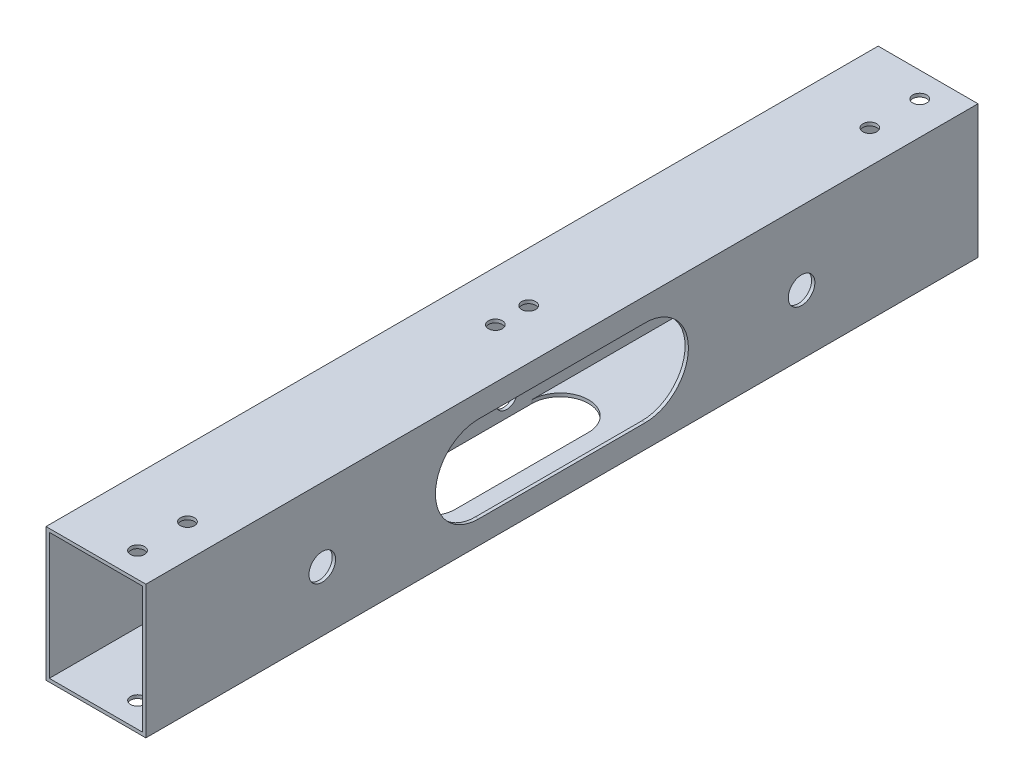
SolidWorks part; units mm, degrees
material "6061 合金"
ref_plane "前视基准面" through (0, 0, 0) normal (0, 0, 1) x (1, 0, 0)
ref_plane "上视基准面" through (0, 0, 0) normal (0, 1, 0) x (1, 0, 0)
ref_plane "右视基准面" through (0, 0, 0) normal (1, 0, 0) x (0, 0, -1)
other "Configuration Table"
sketch "草图1" plane through (0, 0, 0) normal (0, 0, 1) x (1, 0, 0)
  line L0 (15, -20) -> (15, 20)
  line L1 (15, 20) -> (-15, 20)
  line L2 (-15, 20) -> (-15, -20)
  line L3 (-15, -20) -> (15, -20)
  line L4 (14, 19) -> (-14, 19)
  line L5 (14, -19) -> (14, 19)
  line L6 (-14, -19) -> (14, -19)
  line L7 (-14, 19) -> (-14, -19)
extrude "凸台-拉伸1" add sketch "草图1" along normal blind 250
sketch "草图3" plane through (0, 20, 0) normal (0, 1, 0) x (1, 0, 0)
  line L0 (15, 0) -> (-15, 0) construction
  line L2 (-15, -125) -> (78.6025, -125) construction
  line L4 (-15, -250) -> (-15, 0) construction
  circle A0 centre (5, -7.5) radius 2.1
  circle A1 centre (5, -22.5) radius 2.1
  circle A4 centre (5, -227.5) radius 2.1
  circle A5 centre (5, -242.5) radius 2.1
  circle A6 centre (0, -120) radius 2.1
  circle A7 centre (0, -130) radius 2.1
  dimension "D1" = 4.2
  dimension "D2" = 7.5
  dimension "D4" = 20
  dimension "D5" = 4.2
  dimension "D6" = 10
  dimension "D3" = 2
extrude "切除-拉伸1" cut sketch "草图3" against normal blind 250
sketch "草图4" plane through (15, 0, 0) normal (1, 0, 0) x (0, 0, -1)
  line L0 (-250, 20) -> (0, 20) construction
  line L1 (0, -20) -> (0, 20) construction
  line L2 (-125, 20) -> (-125, -104.7599) construction
  circle A0 centre (-53, -2) radius 4
  circle A1 centre (-197, -2) radius 4
  dimension "D1" = 8
  dimension "D2" = 22
  dimension "D3" = 53
extrude "切除-拉伸2" cut sketch "草图4" against normal blind 250
sketch "草图5" plane through (-15, 0, 0) normal (-1, 0, 0) x (0, 0, 1)
  line L0 (250, 20) -> (0, 20) construction
  circle A0 centre (125, -2) radius 7
  dimension "D1" = 22
  dimension "D2" = 14
extrude "切除-拉伸3" cut sketch "草图5" against normal blind 250
sketch "草图6" plane through (0, -20, 0) normal (0, -1, 0) x (1, 0, 0)
  line L0 (-15, 250) -> (-15, 0) construction
  line L2 (-14, 145) -> (-14, 105)
  line L4 (3, 145) -> (3, 105)
  line L5 (-15, 125) -> (57.9688, 125) construction
  line L6 (15, 250) -> (15, 0) construction
  arc A0 (3, 145) -> (-14, 145) centre (-5.5, 145) ccw
  arc A1 (-14, 105) -> (3, 105) centre (-5.5, 105) ccw
  dimension "D4" = 20
  dimension "D5" = 8.5
  dimension "D7" = 20.5
  dimension "D8" = 8.5
  dimension "D1" = 17
  dimension "D2" = 1
  dimension "D3" = 40
  dimension "D6" = 12
extrude "切除-拉伸4" cut sketch "草图6" against normal blind 20
sketch "草图7" plane through (15, 0, 0) normal (1, 0, 0) x (0, 0, -1)
  line L0 (-125, 20) -> (-125, -74.6216) construction
  line L1 (-250, 20) -> (0, 20) construction
  line L2 (-150, 0) -> (-100, 0) construction
  line L3 (-150, 13) -> (-100, 13)
  line L4 (-150, -13) -> (-100, -13)
  arc A0 (-150, 13) -> (-150, -13) centre (-150, 0) ccw
  arc A1 (-100, -13) -> (-100, 13) centre (-100, 0) ccw
  point P8 (-125, 0)
  dimension "D2" = 25
  dimension "D3" = 13
  dimension "D1" = 50
extrude "切除-拉伸6" cut sketch "草图7" against normal blind 22
sketch "草图8" plane through (-15, 0, 0) normal (-1, 0, 0) x (0, 0, 1)
  line L0 (125, 20) -> (125, -55.4072) construction
  line L1 (250, 20) -> (0, 20) construction
  line L2 (250, -20) -> (0, -20) construction
  circle A0 centre (112.625, -14.5) radius 3.25
  circle A1 centre (137.375, -14.5) radius 3.25
  circle A2 centre (112.625, 10.25) radius 3.25
  circle A3 centre (137.375, 10.25) radius 3.25
  dimension "D1" = 24.75
  dimension "D2" = 5.5
  dimension "D4" = 24.75
  dimension "D5" = 6.5
  dimension "D3" = 2
extrude "切除-拉伸7" cut sketch "草图8" against normal blind 22
